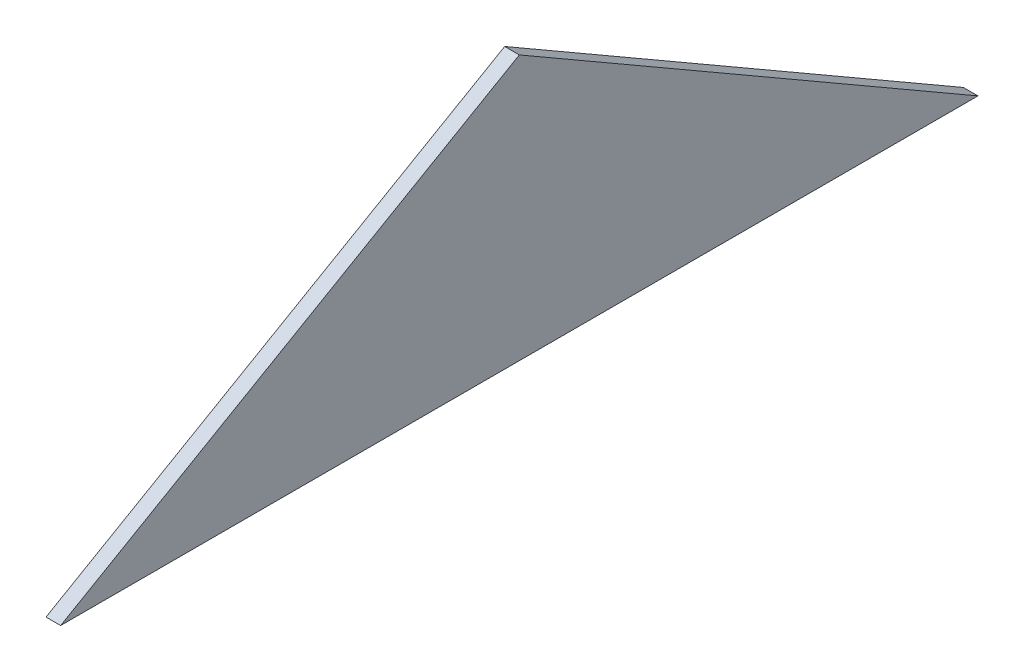
SolidWorks part; units mm, degrees
ref_plane "Front Plane" through (0, 0, 0) normal (0, 0, 1) x (1, 0, 0)
ref_plane "Top Plane" through (0, 0, 0) normal (0, 1, 0) x (1, 0, 0)
ref_plane "Right Plane" through (0, 0, 0) normal (1, 0, 0) x (0, 0, -1)
sketch "Sketch1" plane through (0, 0, 0) normal (1, 0, 0) x (0, 0, -1)
  line L0 (-94, 0) -> (94, 0)
  line L1 (-94, 0) -> (0, 54.2709)
  line L2 (0, 54.2709) -> (94, 0)
  line L3 (-94, 0) -> (-100, 0) construction
  line L4 (-100, 0) -> (0, 57.735) construction
  line L5 (0, 57.735) -> (100, 0) construction
  line L6 (100, 0) -> (94, 0) construction
  point P3 (0, 0)
  point P4 (0, 0)
  point P9 (0, 51.0585)
  point P10 (0, 66.1531)
  point P11 (106.3568, 0)
  dimension "D1" = 3
  dimension "D2" = 30
  dimension "D3" = 200
extrude "Boss-Extrude1" add sketch "Sketch1" along normal blind 3
